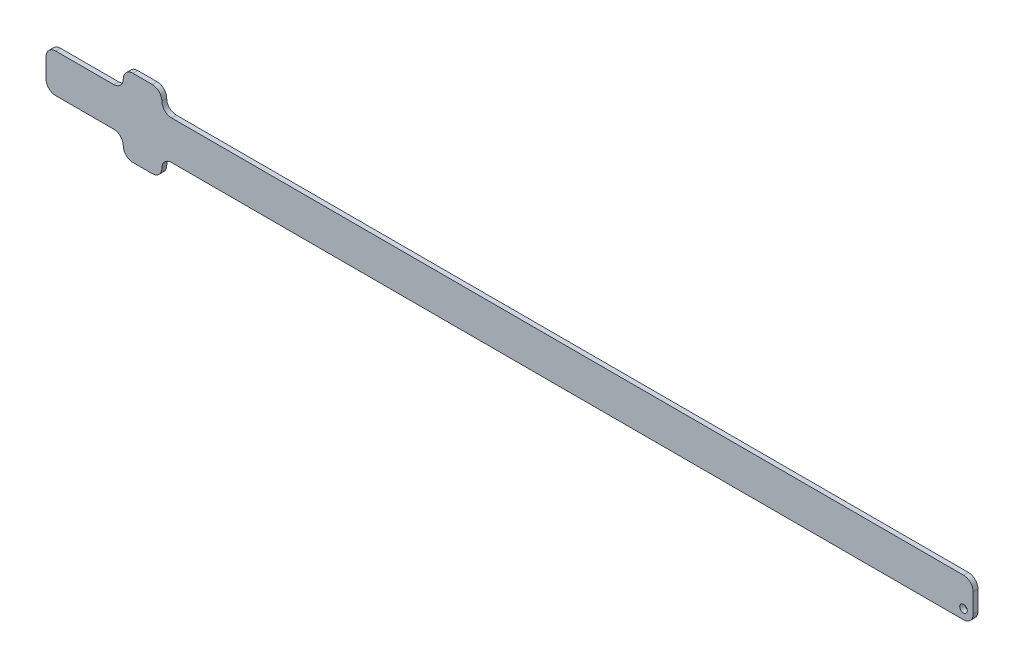
SolidWorks part; units mm, degrees
ref_plane "Front Plane" through (0, 0, 0) normal (0, 0, 1) x (1, 0, 0)
ref_plane "Top Plane" through (0, 0, 0) normal (0, 1, 0) x (1, 0, 0)
ref_plane "Right Plane" through (0, 0, 0) normal (1, 0, 0) x (0, 0, -1)
sketch "Sketch1" plane through (0, 0, 0) normal (0, 0, 1) x (1, 0, 0)
  line L0 (50.8, 0) -> (50.8, -12.7)
  line L1 (0, 0) -> (609.6, 0)
  line L2 (0, 0) -> (0, 25.4)
  line L3 (0, 25.4) -> (609.6, 25.4)
  line L4 (609.6, 0) -> (609.6, 25.4)
  line L5 (50.8, 38.1) -> (76.2, 38.1)
  line L6 (76.2, 38.1) -> (76.2, 25.4)
  line L7 (50.8, 38.1) -> (50.8, 25.4)
  line L8 (76.2, 0) -> (76.2, -12.7)
  line L9 (76.2, -12.7) -> (50.8, -12.7)
  line L11 (609.6, 10.0162) -> (603.25, 13.6823) construction
  line L12 (603.25, 13.6823) -> (596.9, 10.0162) construction
  line L13 (596.9, 10.0162) -> (596.9, 2.6838) construction
  line L14 (596.9, 2.6838) -> (603.25, -0.9823) construction
  line L15 (603.25, -0.9823) -> (609.6, 2.6838) construction
  line L16 (609.6, 2.6838) -> (609.6, 10.0162) construction
  circle A0 centre (603.25, 6.35) radius 2.4892
  circle A1 centre (603.25, 6.35) radius 6.35 construction
  dimension "D5" = 4.9784
  dimension "D6" = 12.7
  dimension "D7" = 12.7
  dimension "D1" = 609.6
  dimension "D2" = 25.4
  dimension "D3" = 25.4
  dimension "D4" = 50.8
extrude "Boss-Extrude1" add sketch "Sketch1" along normal blind 3.175 contours L6 L5 L3 | L1 L4 L3 L2 A0 | L9 L8 L1 region at (63.5, -6.35, 0) region at (304.4243, 12.708, 0) region at (63.5, 31.75, 0)
fillet "Fillet2" radius 6.35 12 edges at (76.2, 38.1, 1.5875) (76.2, 25.4, 1.5875) (609.6, 25.4, 1.5875) (609.6, 0, 1.5875) (76.2, 0, 1.5875) (76.2, -12.7, 1.5875) (50.8, -12.7, 1.5875) (50.8, 0, 1.5875) (0, 0, 1.5875) (50.8, 38.1, 1.5875) (50.8, 25.4, 1.5875) (0, 25.4, 1.5875)
